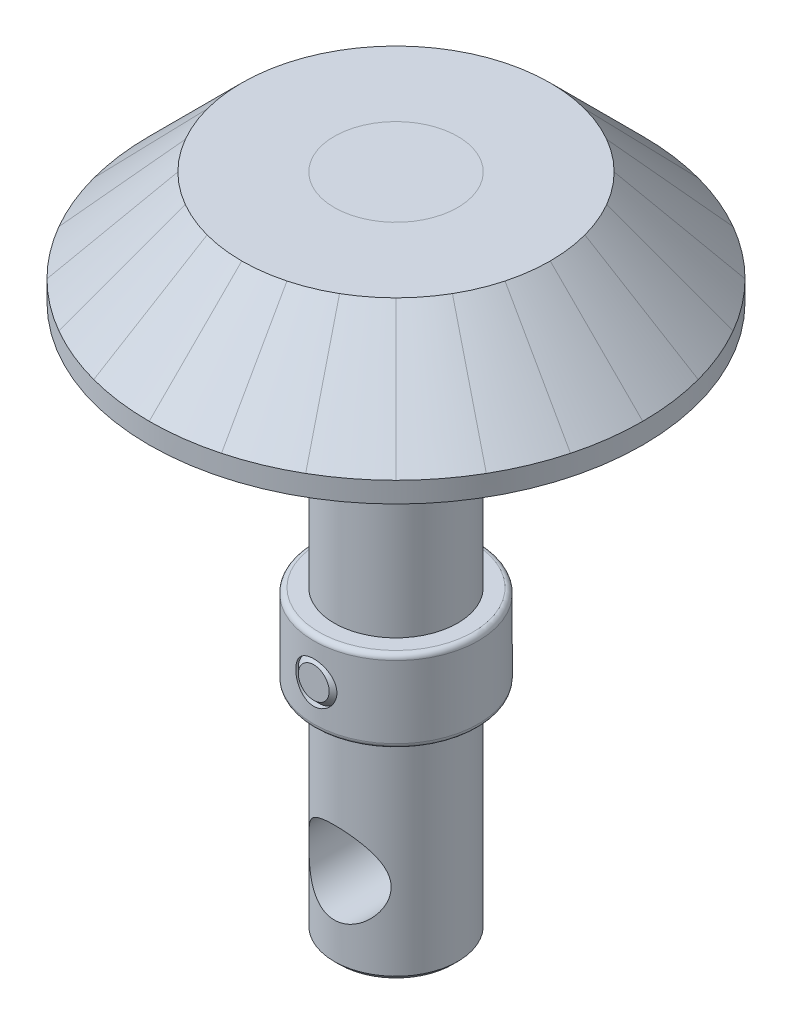
SolidWorks part; units mm, degrees
ref_plane "Front Plane" through (0, 0, 0) normal (0, 0, 1) x (1, 0, 0)
ref_plane "Top Plane" through (0, 0, 0) normal (0, 1, 0) x (1, 0, 0)
ref_plane "Right Plane" through (0, 0, 0) normal (1, 0, 0) x (0, 0, -1)
sketch "Sketch2" plane through (0, 0, 0) normal (0, 1, 0) x (1, 0, 0)
  circle A0 centre (0, 0) radius 3
  dimension "D1" = 6
extrude "Boss-Extrude1" add sketch "Sketch2" along normal blind 32
sketch "Sketch4" plane through (0, 0, 0) normal (1, 0, 0) x (0, 0, -1)
  line L0 (3, 14.5) -> (4, 14.5)
  line L1 (4, 14.5) -> (4, 10.5)
  line L2 (4, 10.5) -> (3, 10.5)
  line L3 (3, 0) -> (3, 32) construction
  line L4 (3, 10.5) -> (3, 14.5)
  line L5 (3, 0) -> (3, 32) construction
  point P11 (3, 12.5)
  dimension "D1" = 4
  dimension "D2" = 4
  dimension "D3" = 12.5
revolve "Revolve1" add sketch "Sketch4" angle 360 about axis through (0, 32, 0) along (0, -1, 0)
sketch "Sketch3" plane through (0, 0, 0) normal (0, 0, 1) x (1, 0, 0)
  circle A0 centre (0, 4) radius 2
  circle A1 centre (0, 12.5) radius 1
  circle A2 centre (0, 25) radius 1
  dimension "D4" = 4
  dimension "D5" = 2
  dimension "D6" = 2
  dimension "D1" = 4
  dimension "D2" = 8.5
  dimension "D3" = 12.5
extrude "Boss-Extrude2" add sketch "Sketch3<3>" along normal mid plane 10.5 separate body contours A2 region at (0, 25, 0)
sketch "Sketch3<3>" plane through (0, 0, 0) normal (0, 0, 1) x (1, 0, 0) same geometry as "Sketch3"
extrude "Boss-Extrude3" add sketch "Sketch3<4>" along normal mid plane 8 separate body contours A1 region at (0, 12.5, 0)
sketch "Sketch3<4>" plane through (0, 0, 0) normal (0, 0, 1) x (1, 0, 0) same geometry as "Sketch3"
extrude "Cut-Extrude1" cut sketch "Sketch3" against normal through all both and the other way through all
sketch "Sketch8" plane through (0, 0, 0) normal (0, 0, 1) x (1, 0, 0)
  line L0 (-3, 26.5) -> (-3, 23.5)
  line L1 (-3, 32) -> (-3, 0) construction
  line L2 (-3, 23.5) -> (-5, 23.5)
  line L3 (-5, 23.5) -> (-5, 26.5)
  line L4 (-3, 26.5) -> (-12, 26.5)
  line L5 (-12, 26.5) -> (-12, 27.5)
  line L6 (-12, 27.5) -> (-7.5, 32)
  line L7 (-7.5, 32) -> (-3, 32)
  line L8 (-12, 27.5) -> (-3, 27.5)
  line L9 (-3, 32) -> (-3, 26.5)
  point P4 (-3, 25)
  point P11 (0, 25)
  dimension "D1" = 3
  dimension "D2" = 5
  dimension "D3" = 12
  dimension "D4" = 4.5
  dimension "D5" = 45
  dimension "D6" = 1
revolve "Revolve5" add sketch "Sketch8" angle 360 about axis through (0, 32, 0) along (0, -1, 0) region at (-4, 25, 0) region at (-7.5, 27, 0) region at (-6.5, 29.5, 0)
extrude "Cut-Extrude2" cut sketch "Sketch3<5>" against normal through all both and the other way through all
sketch "Sketch3<5>" plane through (0, 0, 0) normal (0, 0, 1) x (1, 0, 0) same geometry as "Sketch3"
extrude "Boss-Extrude5" add sketch "Sketch3<7>" along normal mid plane 8 separate body contours A1 region at (0, 12.5, 0)
sketch "Sketch3<7>" plane through (0, 0, 0) normal (0, 0, 1) x (1, 0, 0) same geometry as "Sketch3"
sketch "Sketch9" plane through (0, 32, 0) normal (0, 1, 0) x (1, 0, 0)
  line L0 (0, 7.5) -> (0, 12)
  line L1 (0, 4.899) -> (0, 2.8284) construction
  line L2 (1.9411, 7.2444) -> (3.1058, 11.5911)
  line L3 (3.75, 6.4952) -> (6, 10.3923)
  line L4 (5.3033, 5.3033) -> (8.4853, 8.4853)
  line L5 (6.4952, 3.75) -> (10.3923, 6)
  line L6 (7.2444, 1.9411) -> (11.5911, 3.1058)
  line L7 (7.5, 0) -> (12, 0)
  line L8 (7.2444, -1.9411) -> (11.5911, -3.1058)
  line L9 (6.4952, -3.75) -> (10.3923, -6)
  line L10 (5.3033, -5.3033) -> (8.4853, -8.4853)
  line L11 (3.75, -6.4952) -> (6, -10.3923)
  line L12 (1.9411, -7.2444) -> (3.1058, -11.5911)
  line L13 (0, -7.5) -> (0, -12)
  line L14 (-1.9411, -7.2444) -> (-3.1058, -11.5911)
  line L15 (-3.75, -6.4952) -> (-6, -10.3923)
  line L16 (-5.3033, -5.3033) -> (-8.4853, -8.4853)
  line L17 (-6.4952, -3.75) -> (-10.3923, -6)
  line L18 (-7.2444, -1.9411) -> (-11.5911, -3.1058)
  line L19 (-7.5, 0) -> (-12, 0)
  line L20 (-7.2444, 1.9411) -> (-11.5911, 3.1058)
  line L21 (-6.4952, 3.75) -> (-10.3923, 6)
  line L22 (-5.3033, 5.3033) -> (-8.4853, 8.4853)
  line L23 (-3.75, 6.4952) -> (-6, 10.3923)
  line L24 (-1.9411, 7.2444) -> (-3.1058, 11.5911)
  circle A0 centre (0, 0) radius 7.5 construction
  circle A1 centre (0, 0) radius 12 construction
  point P57 (0, 0)
  dimension "D1" = 24
split line "Split Line1"
fillet "Fillet1" radius 0.25 2 edges at (0, 10.5, 4) (0, 14.5, 4)
chamfer "Chamfer1" distance 0.25 angle 45 2 edges at (1, 12.5, -4) (1, 12.5, 4)
chamfer "Chamfer2" distance 0.25 angle 45 2 edges at (1, 25, 5.25) (1, 25, -5.25)
chamfer "Chamfer3" distance 0.25 angle 45 1 edges at (0, 0, 3)
